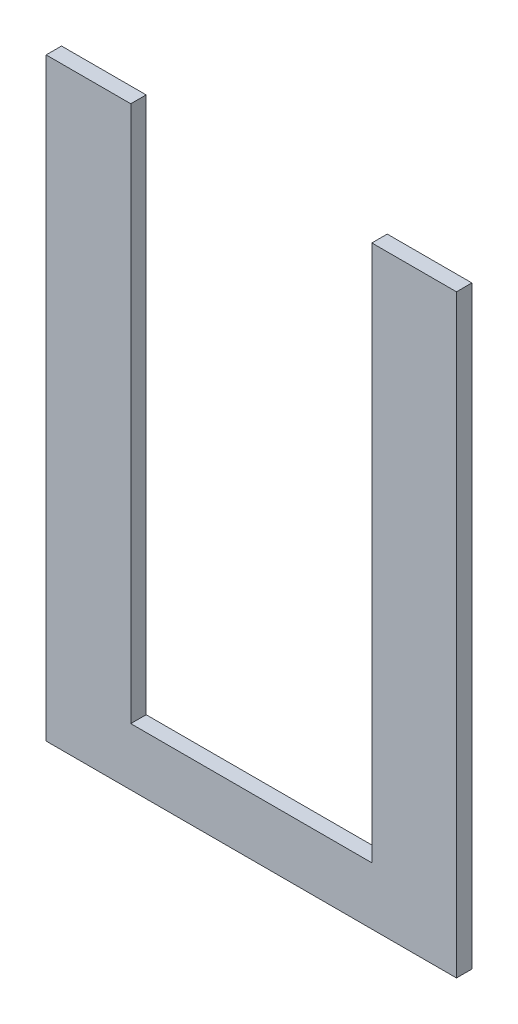
SolidWorks part; units mm, degrees
ref_plane "Front Plane" through (0, 0, 0) normal (0, 0, 1) x (1, 0, 0)
ref_plane "Top Plane" through (0, 0, 0) normal (0, 1, 0) x (1, 0, 0)
ref_plane "Right Plane" through (0, 0, 0) normal (1, 0, 0) x (0, 0, -1)
sketch "Sketch1" plane through (0, 0, 0) normal (0, 0, 1) x (1, 0, 0)
  line L0 (16.5, 11.2) -> (63.5, 11.2) construction
  line L1 (0, 0) -> (80, 0)
  line L2 (0, 0) -> (0, 115.857)
  line L3 (0, 115.857) -> (80, 115.857) construction
  line L4 (80, 0) -> (80, 115.857)
  line L5 (16.5, 115.857) -> (16.5, 11.2) construction
  line L6 (63.5, 11.2) -> (63.5, 115.857) construction
  line L7 (16.5, 11.2) -> (63.5, 11.2)
  line L8 (16.5, 115.857) -> (16.5, 11.2)
  line L9 (63.5, 11.2) -> (63.5, 115.857)
  line L10 (40, 115.857) -> (40, 0) construction
  line L11 (0, 115.857) -> (16.5, 115.857)
  line L12 (63.5, 115.857) -> (80, 115.857)
sketch "Sketch2" plane through (0, 0, 0) normal (0, 1, 0) x (1, 0, 0)
  line L1 (0, 0) -> (80, 0)
  line L2 (0, 0) -> (0, 3)
  line L3 (0, 3) -> (80, 3)
  line L4 (80, 0) -> (80, 3)
extrude "Boss-Extrude1" add sketch "Sketch1" against normal up to vertex (3 mm away) up to point (80, 0, -3)
